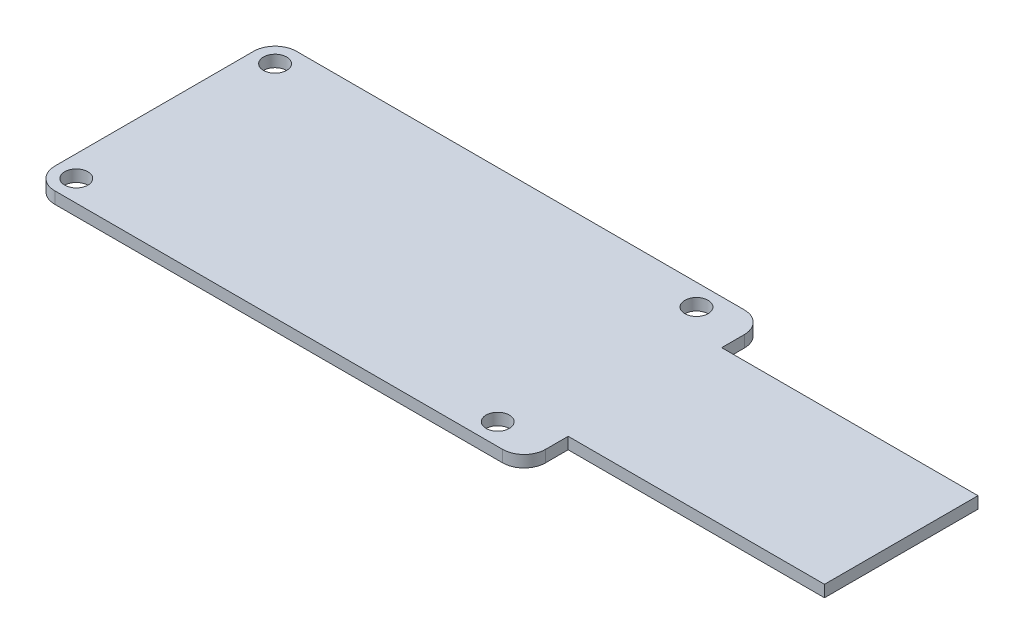
SolidWorks part; units mm, degrees
ref_plane "Front Plane" through (0, 0, 0) normal (0, 0, 1) x (1, 0, 0)
ref_plane "Top Plane" through (0, 0, 0) normal (0, 1, 0) x (1, 0, 0)
ref_plane "Right Plane" through (0, 0, 0) normal (1, 0, 0) x (0, 0, -1)
sketch "Sketch1" plane through (0, 0, 0) normal (0, 1, 0) x (1, 0, 0)
  line L0 (0, 0) -> (0, 27.9326) construction
  line L1 (-33.5, 13.57) -> (-33.5, -13.57)
  line L2 (-30.57, 16.5) -> (30.57, 16.5)
  line L3 (33.5, 13.57) -> (33.5, 10.48)
  line L4 (-30.57, -16.5) -> (30.57, -16.5)
  line L5 (0, 0) -> (-51.5102, 0) construction
  line L6 (-30.57, 13.57) -> (26.97, 13.57) construction
  line L7 (-30.57, 13.57) -> (-30.57, -13.57) construction
  line L8 (-30.57, -13.57) -> (26.97, -13.57) construction
  line L9 (26.97, 13.57) -> (26.97, -13.57) construction
  line L10 (33.5, 10.48) -> (68.5, 10.48)
  line L11 (68.5, 10.48) -> (68.5, -10.48)
  line L12 (68.5, -10.48) -> (33.5, -10.48)
  line L13 (33.5, -10.48) -> (33.5, -13.57)
  circle A0 centre (-30.57, 13.57) radius 1.5875
  circle A1 centre (26.97, 13.57) radius 1.5875
  circle A2 centre (26.97, -13.57) radius 1.5875
  circle A3 centre (-30.57, -13.57) radius 1.5875
  arc A4 (-33.5, 13.57) -> (-30.57, 16.5) centre (-30.57, 13.57) cw
  arc A5 (30.57, 16.5) -> (33.5, 13.57) centre (30.57, 13.57) cw
  arc A6 (33.5, -13.57) -> (30.57, -16.5) centre (30.57, -13.57) cw
  arc A7 (-30.57, -16.5) -> (-33.5, -13.57) centre (-30.57, -13.57) cw
  point P4 (-33.5, 0)
  point P26 (26.97, -13.57)
  point P27 (26.97, 13.57)
  point P29 (0, 16.5)
  point P31 (68.5, 0)
  dimension "D6" = 3.175
  dimension "D5" = 2.93
  dimension "D1" = 33
  dimension "D2" = 67
  dimension "D3" = 27.14
  dimension "D4" = 57.54
  dimension "D7" = 35
  dimension "D8" = 20.96
extrude "Boss-Extrude1" add sketch "Sketch1" along normal blind 1.6
